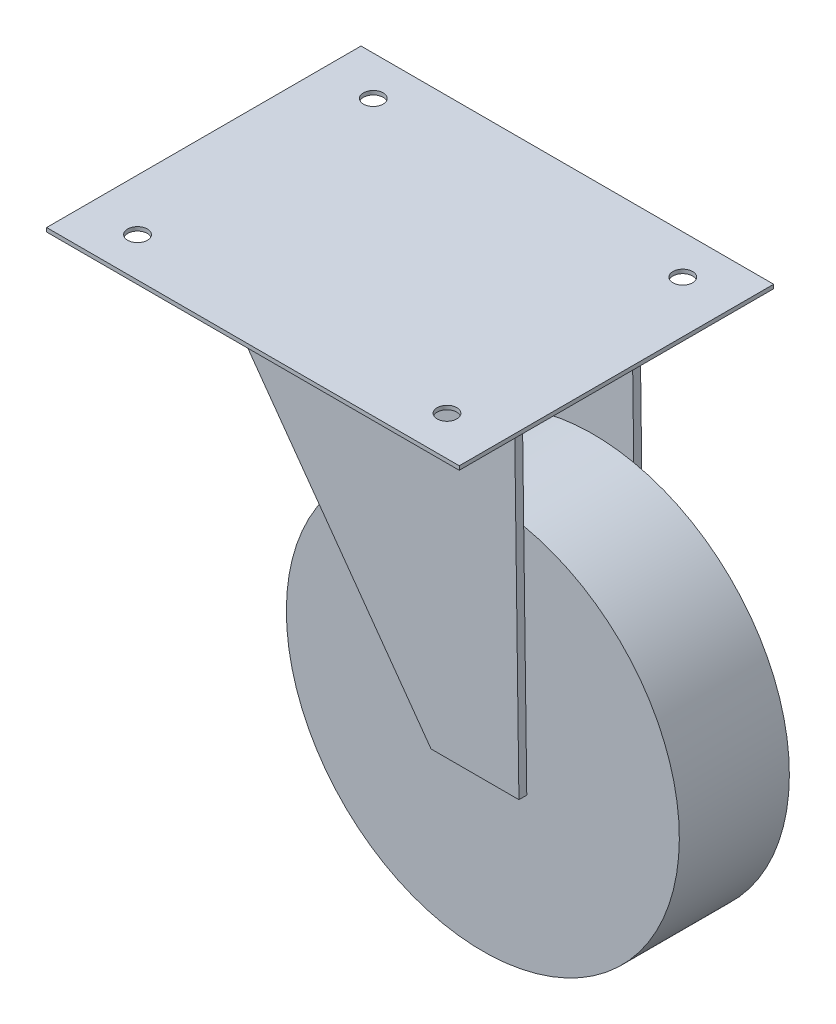
SolidWorks part; units mm, degrees
ref_plane "Спереди" through (0, 0, 0) normal (0, 0, 1) x (1, 0, 0)
ref_plane "Сверху" through (0, 0, 0) normal (0, 1, 0) x (1, 0, 0)
ref_plane "Справа" through (0, 0, 0) normal (1, 0, 0) x (0, 0, -1)
sketch "Эскиз1" plane through (0, 0, 0) normal (0, 1, 0) x (1, 0, 0)
  line L1 (-52.5, -40) -> (52.5, -40)
  line L2 (-52.5, -40) -> (-52.5, 40)
  line L3 (-52.5, 40) -> (52.5, 40)
  line L4 (52.5, -40) -> (52.5, 40)
  line L5 (-52.5, -40) -> (52.5, 40) construction
  line L6 (-52.5, 40) -> (52.5, -40) construction
  circle A0 centre (-39.375, 30) radius 2.5
  circle A1 centre (39.375, 30) radius 2.5
  circle A2 centre (39.375, -30) radius 2.5
  circle A3 centre (-39.375, -30) radius 2.5
  point P0 (0, 0)
  point P14 (0, 0)
  point P15 (0, 0)
  point P16 (0, 0)
  point P17 (0, 0)
  point P18 (-39.375, -30)
  dimension "D3" = 60
  dimension "D4" = 5
  dimension "D5" = 5
  dimension "D6" = 5
  dimension "D7" = 5
  dimension "D1" = 105
  dimension "D2" = 80
extrude "Бобышка-Вытянуть1" add sketch "Эскиз1" along normal blind 1
sketch "Эскиз2" plane through (0, 0, 0) normal (0, 0, 1) x (1, 0, 0)
  line L0 (82.5, 23.5045) -> (82.5, -115.2638) construction
  line L1 (-52.5, 1) -> (-52.5, 0) construction
  line L2 (-46.046, -129) -> (131.9496, -129) construction
  line L3 (-52.5, 1) -> (52.5, 1) construction
  circle A0 centre (32.5, -79) radius 50
  dimension "D1" = 100
  dimension "D2" = 135
  dimension "D3" = 130
extrude "Бобышка-Вытянуть2" add sketch "Эскиз2" along normal blind 28 from offset 14 separate body offset against normal yes
sketch "Эскиз3" plane through (0, 0, 14) normal (0, 0, 1) x (1, 0, 0)
  line L0 (21.3197, -89) -> (43.6803, -89)
  line L1 (43.6803, -89) -> (42.5, 0)
  line L2 (-52.5, 0) -> (52.5, 0) construction
  line L3 (42.5, 0) -> (-42.5, 0)
  line L4 (-42.5, 0) -> (21.3197, -89)
  line L5 (-17.5, -79) -> (82.5, -79) construction
  circle A0 centre (32.5, -79) radius 50 construction
  point P13 (32.5, -79)
  dimension "D1" = 10
  dimension "D2" = 10
  dimension "D3" = 10
  dimension "D4" = 15
  dimension "D5" = 15
extrude "Бобышка-Вытянуть3" add sketch "Эскиз3" along normal blind 2
pattern_linear "Линейный массив1" count 2 spacing 30 along (0, 0, -1) of "Бобышка-Вытянуть3"
